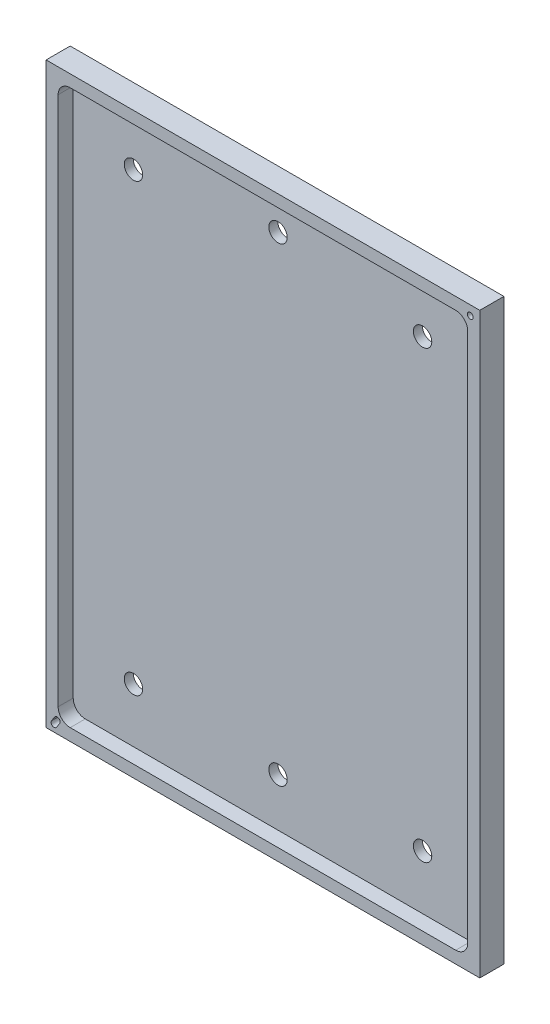
SolidWorks part; units mm, degrees
material "AISI 304"
ref_plane "Front Plane" through (0, 0, 0) normal (0, 0, 1) x (1, 0, 0)
ref_plane "Top Plane" through (0, 0, 0) normal (0, 1, 0) x (1, 0, 0)
ref_plane "Right Plane" through (0, 0, 0) normal (1, 0, 0) x (0, 0, -1)
sketch "Sketch1" plane through (0, 0, 0) normal (0, 0, 1) x (1, 0, 0)
  line L1 (114.3, -152.4) -> (-114.3, -152.4)
  line L2 (114.3, -152.4) -> (114.3, 152.4)
  line L3 (114.3, 152.4) -> (-114.3, 152.4)
  line L4 (-114.3, -152.4) -> (-114.3, 152.4)
  line L5 (114.3, -152.4) -> (-114.3, 152.4) construction
  line L6 (114.3, 152.4) -> (-114.3, -152.4) construction
  point P0 (0, 0)
  dimension "D1" = 228.6
  dimension "D2" = 304.8
extrude "Boss-Extrude1" add sketch "Sketch1" along normal blind 12.7
sketch "Sketch2" plane through (0, 0, 12.7) normal (0, 0, 1) x (1, 0, 0)
  line L0 (-114.3, 152.4) -> (-114.3, -152.4) construction
  line L1 (101.6, -146.05) -> (-101.6, -146.05)
  line L2 (107.95, -139.7) -> (107.95, 139.7)
  line L3 (101.6, 146.05) -> (-101.6, 146.05)
  line L4 (-107.95, -139.7) -> (-107.95, 139.7)
  line L5 (107.95, -146.05) -> (-107.95, 146.05) construction
  line L6 (107.95, 146.05) -> (-107.95, -146.05) construction
  line L7 (114.3, 152.4) -> (-114.3, 152.4) construction
  arc A0 (-101.6, -146.05) -> (-107.95, -139.7) centre (-101.6, -139.7) cw
  arc A1 (101.6, -146.05) -> (107.95, -139.7) centre (101.6, -139.7) ccw
  arc A2 (107.95, 139.7) -> (101.6, 146.05) centre (101.6, 139.7) ccw
  arc A3 (-101.6, 146.05) -> (-107.95, 139.7) centre (-101.6, 139.7) ccw
  point P0 (0, 0)
  dimension "D3" = 6.35
  dimension "D1" = 6.35
  dimension "D2" = 6.35
extrude "Cut-Extrude1" cut sketch "Sketch2" against normal blind 7.9375
sketch "Sketch4" plane through (0, 0, 4.7625) normal (0, 0, 1) x (1, 0, 0)
  line L0 (114.3, 152.4) -> (-114.3, 152.4) construction
  line L4 (-114.3, 152.4) -> (-114.3, -152.4) construction
  line L5 (114.3, -152.4) -> (114.3, 152.4) construction
  line L6 (-114.3, -152.4) -> (114.3, -152.4) construction
  line L8 (-101.6, -146.05) -> (101.6, -146.05) construction
  circle A0 centre (-76.2, 117.4) radius 4.85
  circle A1 centre (76.2, 117.4) radius 4.85
  circle A2 centre (-76.2, -117.4) radius 4.85
  circle A3 centre (76.2, -117.4) radius 4.85
  circle A4 centre (0, 126.925) radius 4.85
  circle A5 centre (0, -120.65) radius 4.85
  dimension "D1" = 9.7
  dimension "D2" = 9.7
  dimension "D3" = 9.7
  dimension "D4" = 9.7
  dimension "D13" = 9.7
  dimension "D14" = 9.7
  dimension "D15" = 35
  dimension "D5" = 9.525
  dimension "D6" = 38.1
  dimension "D7" = 38.1
  dimension "D8" = 0
  dimension "D9" = 35
  dimension "D10" = 38.1
  dimension "D11" = 38.1
  dimension "D12" = 35
  dimension "D16" = 25.4
extrude "Cut-Extrude2" cut sketch "Sketch4" against normal through all
hole_wizard "Ø3.1 (3.1) Diameter Hole1" positions "Sketch5" profile "Sketch6" hole size "Ø3.1" standard "ANSI Metric"
sketch "Sketch5" plane through (0, 0, 12.7) normal (0, 0, 1) x (1, 0, 0)
  line L0 (114.3, 152.4) -> (-114.3, 152.4) construction
  line L1 (114.3, -152.4) -> (114.3, 152.4) construction
  point P0 (109.3, 147.4)
  dimension "D1" = 5
  dimension "D2" = 5
sketch "Sketch6" plane through (109.3, 147.4, 12.7) normal (1, 0, 0) x (0, -1, 0)
  line L0 (0, 0) -> (0, 5.9313)
  line L1 (0, 5.9313) -> (1.55, 5)
  line L2 (1.55, 5) -> (1.55, 0)
  line L5 (1.55, 0) -> (0, 0)
  line L10 (0, 5.9313) -> (-1.55, 5) construction
  line L11 (0, -6.35) -> (0, 107.95) construction
  dimension "Hole Dia." = 3.1
  dimension "Hole Depth" = 5
  dimension "Drill Angle" = 118
sketch "Sketch7" plane through (0, 0, 12.7) normal (0, 0, 1) x (1, 0, 0)
  line L0 (-110.1279, -148.6508) -> (-108.4721, -146.1492) construction
  line L1 (-111.4204, -147.7953) -> (-109.7646, -145.2937)
  line L2 (-108.8354, -149.5063) -> (-107.1796, -147.0047)
  line L3 (-114.3, -152.4) -> (114.3, -152.4) construction
  line L4 (-114.3, 152.4) -> (-114.3, -152.4) construction
  arc A0 (-111.4204, -147.7953) -> (-108.8354, -149.5063) centre (-110.1279, -148.6508) ccw
  arc A1 (-107.1796, -147.0047) -> (-109.7646, -145.2937) centre (-108.4721, -146.1492) ccw
  point P2 (-109.3, -147.4)
  point P7 (-110.5925, -146.5445)
  dimension "D1" = 3
  dimension "D2" = 3.1
  dimension "D3" = 5
  dimension "D4" = 5
  dimension "D5" = 56.5
extrude "Cut-Extrude3" cut sketch "Sketch7" against normal blind 5
hole_wizard "M4x0.7 Tapped Hole1" positions "Sketch8" profile "Sketch9" tap size "M4x0.7" standard "ANSI Metric"
sketch "Sketch8" plane through (0, 0, 0) normal (0, 0, -1) x (-1, 0, 0)
  line L0 (114.3, -152.4) -> (-114.3, -152.4) construction
  line L1 (-114.3, -152.4) -> (-114.3, 152.4) construction
  point P0 (-111.125, -102.4)
  point P2 (-111.125, 0)
  point P4 (-111.125, 113.6)
  point P14 (-114.3, 0)
  dimension "D1" = 266
  dimension "D2" = 3.175
  dimension "D3" = 50
sketch "Sketch9" plane through (111.125, -102.4, 0) normal (1, 0, 0) x (0, 1, 0)
  line L0 (0, 0) -> (0, 6.3914)
  line L1 (0, 6.3914) -> (1.65, 5.4)
  line L2 (1.65, 5.4) -> (1.65, 0)
  line L5 (1.65, 0) -> (0, 0)
  line L10 (0, 6.3914) -> (-1.65, 5.4) construction
  line L11 (0, -6.35) -> (0, 107.95) construction
  dimension "Tap Drill Dia." = 3.3
  dimension "Tap Drill Depth" = 5.4
  dimension "Drill Angle" = 118
cosmetic thread "Hole Thread1" parameters "D1"=3, "D2"=4.3
cosmetic thread "Hole Thread2" parameters "D1"=3, "D2"=4.3
cosmetic thread "Hole Thread3" parameters "D1"=3, "D2"=4.3
sketch "Sketch11" plane through (0, 0, 0) normal (0, 0, -1) x (-1, 0, 0)
  line L0 (-114.3, -152.4) -> (-114.3, 152.4) construction
  line L2 (-114.3, 82.4) -> (-126.3, 82.4)
  line L3 (-114.3, 82.4) -> (-114.3, 65.4)
  line L4 (-114.3, 65.4) -> (-126.3, 65.4)
  line L5 (-131.3, 77.4) -> (-131.3, 70.4)
  line L6 (-114.3, 152.4) -> (114.3, 152.4) construction
  line L7 (0, 6.985) -> (0, -6.985) construction
  line L8 (131.3, 77.4) -> (131.3, 70.4)
  line L9 (114.3, 65.4) -> (126.3, 65.4)
  line L10 (114.3, 82.4) -> (114.3, 65.4)
  line L11 (114.3, 82.4) -> (126.3, 82.4)
  line L12 (6.985, 0) -> (-6.985, 0) construction
  line L13 (114.3, -82.4) -> (126.3, -82.4)
  line L14 (114.3, -82.4) -> (114.3, -65.4)
  line L15 (114.3, -65.4) -> (126.3, -65.4)
  line L16 (131.3, -77.4) -> (131.3, -70.4)
  line L17 (-131.3, -77.4) -> (-131.3, -70.4)
  line L18 (-114.3, -65.4) -> (-126.3, -65.4)
  line L19 (-114.3, -82.4) -> (-114.3, -65.4)
  line L20 (-114.3, -82.4) -> (-126.3, -82.4)
  arc A0 (-131.3, 70.4) -> (-126.3, 65.4) centre (-126.3, 70.4) ccw
  arc A1 (-131.3, 77.4) -> (-126.3, 82.4) centre (-126.3, 77.4) cw
  arc A2 (131.3, 77.4) -> (126.3, 82.4) centre (126.3, 77.4) ccw
  arc A3 (131.3, 70.4) -> (126.3, 65.4) centre (126.3, 70.4) cw
  arc A4 (131.3, -70.4) -> (126.3, -65.4) centre (126.3, -70.4) ccw
  arc A5 (131.3, -77.4) -> (126.3, -82.4) centre (126.3, -77.4) cw
  arc A6 (-131.3, -77.4) -> (-126.3, -82.4) centre (-126.3, -77.4) ccw
  arc A7 (-131.3, -70.4) -> (-126.3, -65.4) centre (-126.3, -70.4) cw
  point P6 (-114.3, 61.0313)
  point P11 (-131.3, 65.4)
  point P14 (-131.3, 82.4)
  point P25 (131.3, 82.4)
  point P26 (131.3, 65.4)
  point P45 (131.3, -65.4)
  point P46 (131.3, -82.4)
  point P47 (-131.3, -82.4)
  point P48 (-131.3, -65.4)
  dimension "D4" = 5
  dimension "D1" = 17
  dimension "D2" = 17
  dimension "D3" = 70
extrude "Boss-Extrude2" [suppressed] add sketch "Sketch11" against normal blind 9.525
fillet "Fillet1" [suppressed] radius 3.175
